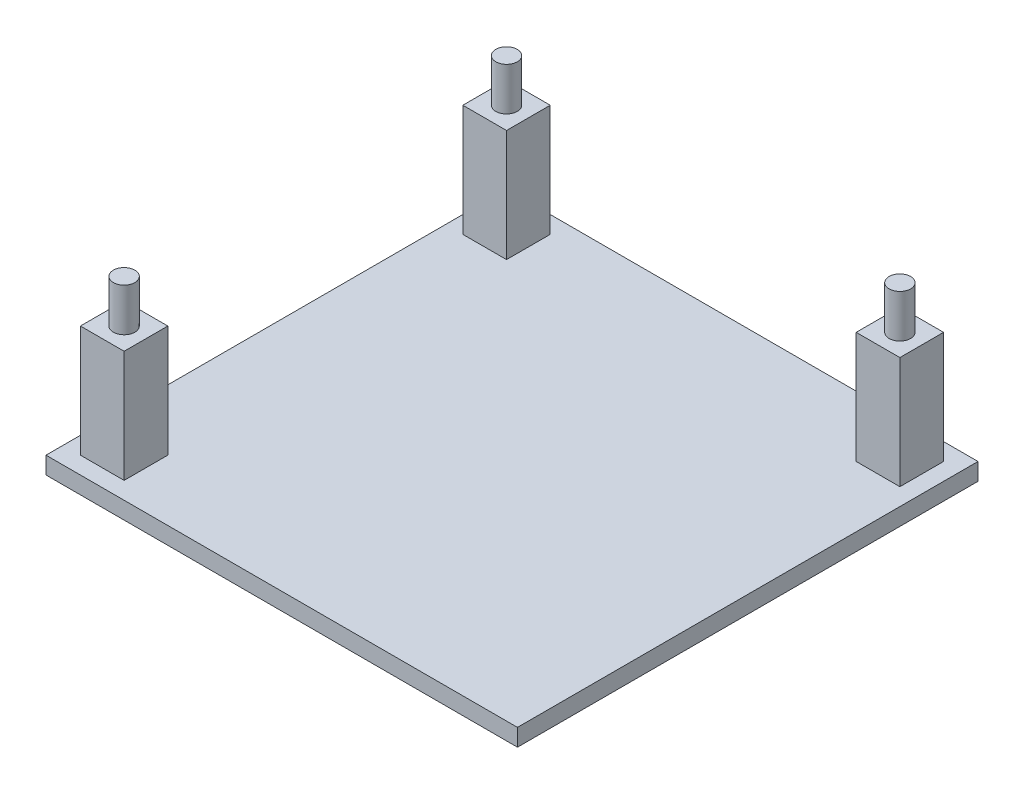
SolidWorks part; units mm, degrees
ref_plane "Front Plane" through (0, 0, 0) normal (0, 0, 1) x (1, 0, 0)
ref_plane "Top Plane" through (0, 0, 0) normal (0, 1, 0) x (1, 0, 0)
ref_plane "Right Plane" through (0, 0, 0) normal (1, 0, 0) x (0, 0, -1)
sketch "Sketch2" plane through (0, 0, 0) normal (0, 1, 0) x (1, 0, 0)
  line L1 (27.4, -26.765) -> (-27.4, -26.765)
  line L2 (27.4, -26.765) -> (27.4, 26.765)
  line L3 (27.4, 26.765) -> (-27.4, 26.765)
  line L4 (-27.4, -26.765) -> (-27.4, 26.765)
  line L5 (27.4, -26.765) -> (-27.4, 26.765) construction
  line L6 (27.4, 26.765) -> (-27.4, -26.765) construction
  point P0 (0, 0)
  dimension "D1" = 54.8
  dimension "D2" = 53.53
extrude "Boss-Extrude1" add sketch "Sketch2" along normal blind 2
sketch "Sketch3" plane through (0, 2, 0) normal (0, 1, 0) x (1, 0, 0)
  line L0 (27.4, 26.765) -> (-27.4, 26.765) construction
  line L1 (-20.32, 19.685) -> (-25.4, 19.685)
  line L2 (-20.32, 19.685) -> (-20.32, 24.765)
  line L3 (-20.32, 24.765) -> (-25.4, 24.765)
  line L4 (-25.4, 19.685) -> (-25.4, 24.765)
  line L5 (-20.32, 19.685) -> (-25.4, 24.765) construction
  line L6 (-20.32, 24.765) -> (-25.4, 19.685) construction
  line L7 (-27.4, 26.765) -> (-27.4, -26.765) construction
  line L8 (27.4, -26.765) -> (27.4, 26.765) construction
  line L9 (25.4, 19.685) -> (20.32, 19.685)
  line L10 (25.4, 19.685) -> (25.4, 24.765)
  line L11 (25.4, 24.765) -> (20.32, 24.765)
  line L12 (20.32, 19.685) -> (20.32, 24.765)
  line L13 (25.4, 19.685) -> (20.32, 24.765) construction
  line L14 (25.4, 24.765) -> (20.32, 19.685) construction
  line L15 (-27.4, -26.765) -> (27.4, -26.765) construction
  line L16 (-20.32, -24.765) -> (-25.4, -24.765)
  line L17 (-20.32, -24.765) -> (-20.32, -19.685)
  line L18 (-20.32, -19.685) -> (-25.4, -19.685)
  line L19 (-25.4, -24.765) -> (-25.4, -19.685)
  line L20 (-20.32, -24.765) -> (-25.4, -19.685) construction
  line L21 (-20.32, -19.685) -> (-25.4, -24.765) construction
  point P0 (-22.86, 22.225)
  point P7 (22.86, 22.225)
  point P16 (-22.86, -22.225)
  dimension "D1" = 2
  dimension "D2" = 2
  dimension "D3" = 5.08
  dimension "D4" = 5.08
  dimension "D5" = 5.08
  dimension "D6" = 5.08
  dimension "D7" = 2
  dimension "D8" = 2
  dimension "D9" = 2
  dimension "D10" = 2
  dimension "D11" = 5.08
  dimension "D12" = 5.08
extrude "Boss-Extrude2" add sketch "Sketch3" along normal blind 13
sketch "Sketch6" plane through (0, 15, 0) normal (0, 1, 0) x (1, 0, 0)
  line L1 (-25.4, 19.685) -> (-20.32, 19.685) construction
  line L3 (-25.4, 24.765) -> (-25.4, 19.685) construction
  line L4 (20.32, 24.765) -> (20.32, 19.685) construction
  line L5 (20.32, 19.685) -> (25.4, 19.685) construction
  line L6 (-20.32, -24.765) -> (-20.32, -19.685) construction
  line L8 (-25.4, -24.765) -> (-20.32, -24.765) construction
  circle A0 centre (-22.86, 22.225) radius 1.25
  circle A1 centre (22.86, 22.225) radius 1.25
  circle A2 centre (-22.86, -22.225) radius 1.25
  point P10 (22.86, 19.685)
  point P17 (-22.86, -24.765)
  point P19 (-23.8579, -25.765)
  dimension "D1" = 2.54
  dimension "D3" = 2.54
  dimension "D5" = 2.54
  dimension "D2" = 2.54
  dimension "D4" = 2.54
  dimension "D6" = 2.54
extrude "Boss-Extrude3" add sketch "Sketch6" along normal blind 5
